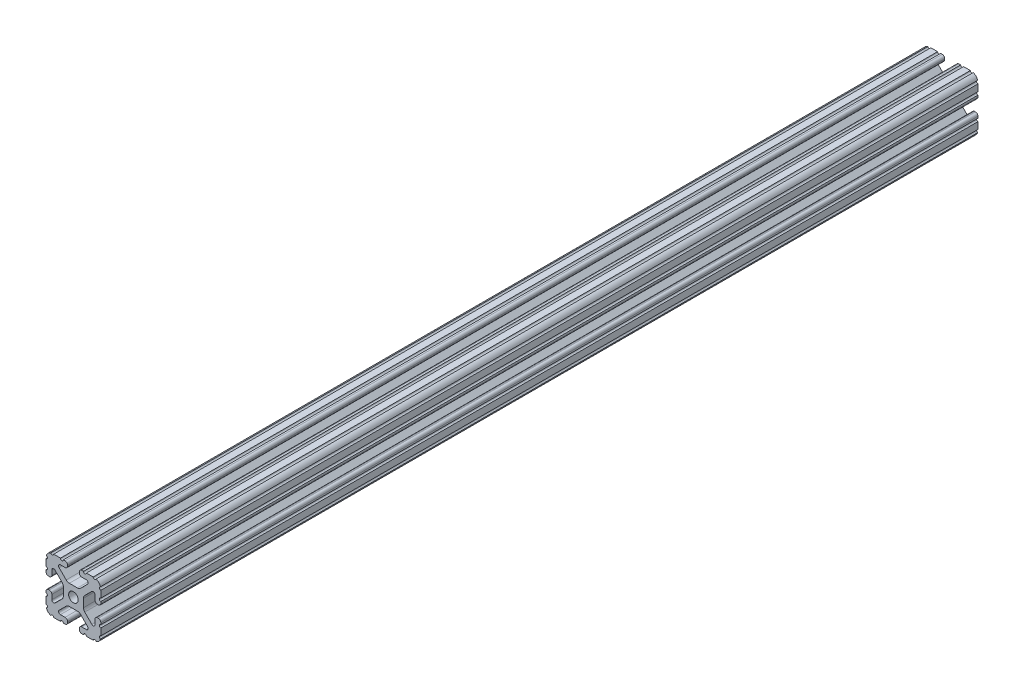
SolidWorks part; units mm, degrees
ref_plane "Front Plane" through (0, 0, 0) normal (0, 0, 1) x (1, 0, 0)
ref_plane "Top Plane" through (0, 0, 0) normal (0, 1, 0) x (1, 0, 0)
ref_plane "Right Plane" through (0, 0, 0) normal (1, 0, 0) x (0, 0, -1)
sketch "Sketch2" plane through (0, 0, 0) normal (0, 0, 1) x (1, 0, 0)
  line L0 (0, 19.05) -> (0, -19.05) construction
  line L1 (-19.05, 0) -> (19.05, 0) construction
  line L2 (4.064, -19.05) -> (19.05, -19.05)
  line L3 (19.05, -19.05) -> (19.05, -4.064)
  line L4 (4.064, -19.05) -> (4.064, -14.986)
  line L5 (4.064, -14.986) -> (12.1123, -14.986)
  line L6 (12.1123, -14.986) -> (4.1113, -6.985)
  line L7 (0, 0) -> (19.05, -19.05) construction
  line L8 (19.05, -4.064) -> (14.986, -4.064)
  line L9 (14.986, -4.064) -> (14.986, -12.1123)
  line L10 (14.986, -12.1123) -> (6.985, -4.1113)
  circle A0 centre (0, 0) radius 3.3274
  arc A1 (8.9963, -14.986) -> (9.909, -12.7826) centre (8.9963, -13.6953) ccw construction
  point P8 (0, -6.985)
  dimension "Center Hole Diameter" = 6.6548
  dimension "Rail Height" = 38.1
  dimension "Rail Width" = 38.1
  dimension "T-Slot Width" = 8.128
  dimension "Slot Inner Width" = 20.574
  dimension "Thickness" = 4.064
  dimension "Slot Depth" = 8.001
  dimension "D1" = 4.064
sketch "Sketch3" plane through (0, 0, 0) normal (1, 0, 0) x (0, 0, -1)
  line L0 (-304.8, -19.05) -> (304.8, -19.05) construction
  line L1 (-279.4, 0) -> (279.4, 0) construction
  dimension "Length" = 609.6
  dimension "D1" = 25.4
sketch "Sketch4" plane through (0, 0, 0) normal (0, 0, 1) x (1, 0, 0)
  line L0 (5.7912, -19.05) -> (14.3002, -19.05)
  line L1 (4.064, -19.05) -> (19.05, -19.05) construction
  line L2 (4.064, -19.05) -> (4.064, -14.986) construction
  line L3 (4.064, -14.986) -> (12.1123, -14.986) construction
  line L4 (4.064, -16.7132) -> (4.064, -17.3228)
  line L5 (5.7912, -14.986) -> (8.9963, -14.986)
  line L6 (0, -6.985) -> (2.833, -6.985)
  line L7 (12.1123, -14.986) -> (4.1113, -6.985) construction
  line L8 (5.0152, -7.8889) -> (9.909, -12.7826)
  line L9 (19.05, -19.05) -> (19.05, -4.064) construction
  line L10 (14.986, -12.1123) -> (6.985, -4.1113) construction
  line L11 (14.986, -4.064) -> (14.986, -12.1123) construction
  line L12 (14.986, -8.9963) -> (14.986, -5.7912)
  line L13 (19.05, -4.064) -> (14.986, -4.064) construction
  line L14 (16.7132, -4.064) -> (17.3228, -4.064)
  line L15 (19.05, -5.7912) -> (19.05, -14.3002)
  line L16 (12.7826, -9.909) -> (7.8889, -5.0152)
  line L17 (6.985, 0) -> (6.985, -2.833)
  line L18 (-19.05, 0) -> (19.05, 0) construction
  line L19 (0, -6.985) -> (0, -3.3274)
  line L20 (0, 19.05) -> (0, -19.05) construction
  line L21 (6.985, 0) -> (3.3274, 0)
  arc A0 (4.064, -17.3228) -> (5.7912, -19.05) centre (5.7912, -17.3228) ccw
  arc A2 (4.064, -16.7132) -> (5.7912, -14.986) centre (5.7912, -16.7132) cw
  arc A3 (8.9963, -14.986) -> (9.909, -12.7826) centre (8.9963, -13.6953) ccw
  arc A4 (2.833, -6.985) -> (5.0152, -7.8889) centre (2.833, -10.0711) cw
  arc A5 (14.3002, -19.05) -> (19.05, -14.3002) centre (14.3002, -14.3002) ccw
  arc A6 (12.7826, -9.909) -> (14.986, -8.9963) centre (13.6953, -8.9963) ccw
  arc A7 (14.986, -5.7912) -> (16.7132, -4.064) centre (16.7132, -5.7912) cw
  arc A8 (17.3228, -4.064) -> (19.05, -5.7912) centre (17.3228, -5.7912) cw
  arc A9 (7.8889, -5.0152) -> (6.985, -2.833) centre (10.0711, -2.833) cw
  circle A10 centre (0, 0) radius 3.3274 construction
  arc A11 (0, -3.3274) -> (3.3274, 0) centre (0, 0) ccw
  dimension "D1" = 4.7498
  dimension "D2" = 3.0861
  dimension "D3" = 1.7272
extrude "Boss-Extrude1" add sketch "Sketch4" along normal mid plane 609.6
sketch "Sketch5" plane through (0, 0, 0) normal (0, 0, 1) x (1, 0, 0)
  line L0 (4.064, -19.05) -> (19.05, -19.05) construction
  line L1 (5.7912, -14.986) -> (8.9963, -14.986) construction
  line L3 (0, 0) -> (19.05, -19.05) construction
  line L4 (8.9963, -14.986) -> (8.9963, -19.05) construction
  line L5 (12.1123, -14.986) -> (4.1113, -6.985) construction
  circle A0 centre (14.7395, -19.05) radius 1.016
  circle A1 centre (7.9803, -19.05) radius 1.016
  circle A2 centre (19.05, -14.7395) radius 1.016
  circle A3 centre (19.05, -7.9803) radius 1.016
  point P10 (7.3938, -14.986)
  point P12 (13.6953, -8.9963)
  dimension "D1" = 2.032
extrude "Cut-Extrude1" cut sketch "Sketch5" against normal through all both and the other way through all
mirror "Mirror1" about plane through (0, 0, 0) normal (1, 0, 0) of bodies 137 134
mirror "Mirror2" about plane through (0, 0, 0) normal (0, 1, 0) of bodies 135
equation "\"D1@Boss-Extrude1\"=\"Length@Sketch3\""
equation "\"D1@Sketch2\"=\"Thickness@Sketch2\""
equation "\"D2@Sketch4\"=\"Slot Inner Width@Sketch2\"*0.15"
equation "\"D1@Sketch4\"=\"D3@Sketch4\"*2.75"
equation "\"D3@Sketch4\"=\"Thickness@Sketch2\"*0.425"
equation "\"D1@Sketch5\"=\"Thickness@Sketch2\"*0.5"
